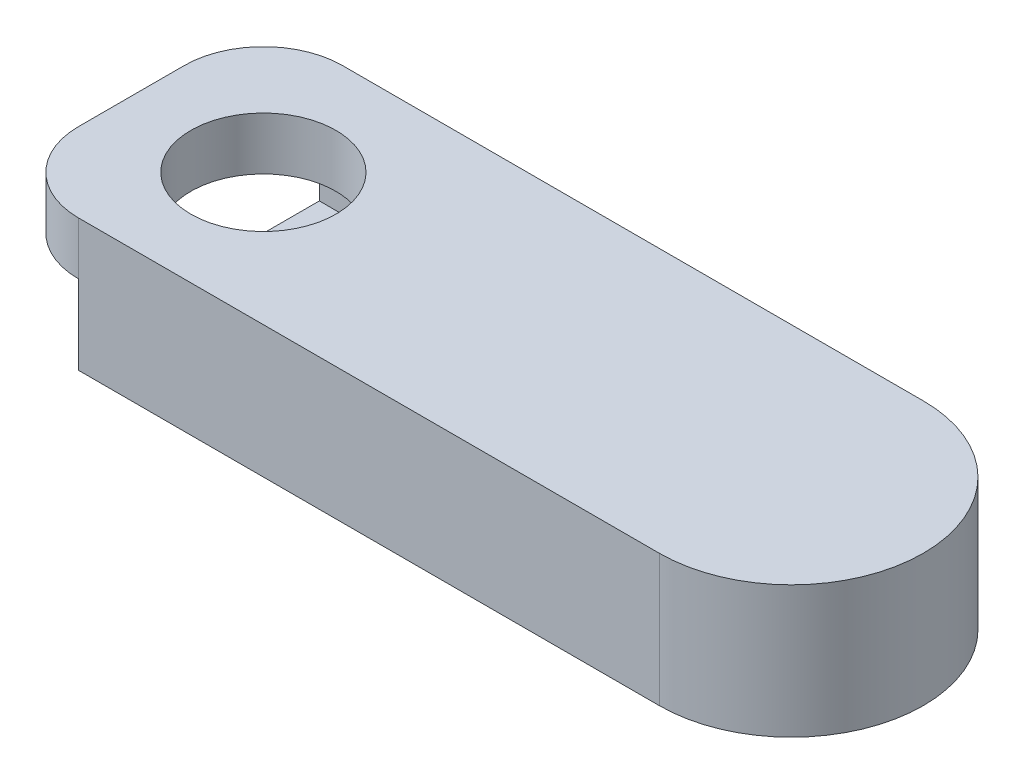
SolidWorks part; units mm, degrees
ref_plane "Front Plane" through (0, 0, 0) normal (0, 0, 1) x (1, 0, 0)
ref_plane "Top Plane" through (0, 0, 0) normal (0, 1, 0) x (1, 0, 0)
ref_plane "Right Plane" through (0, 0, 0) normal (1, 0, 0) x (0, 0, -1)
sketch "Sketch1" plane through (0, 0, 0) normal (0, 1, 0) x (1, 0, 0)
  line L0 (0, 0) -> (-381, 0)
  line L1 (-381, 0) -> (-381, -127)
  line L2 (-381, -127) -> (0, -127)
  line L3 (0, -127) -> (0, 0)
  dimension "D1" = 381
  dimension "D2" = 127
extrude "Boss-Extrude1" add sketch "Sketch1" along normal blind 25.4
fillet "Fillet1" radius 63.5 2 edges at (0, 12.7, 0) (0, 12.7, 127)
fillet "Fillet2" radius 38.1 2 edges at (-381, 12.7, 0) (-381, 12.7, 127)
sketch "Sketch2" plane through (0, 0, 0) normal (0, 1, 0) x (1, 0, 0)
  line L0 (-63.5, -12.7) -> (-342.9, -11.1592)
  line L1 (-342.9, -11.1592) -> (-342.9, 0)
  line L2 (-342.9, 0) -> (-63.5, 0)
  line L3 (-63.5, -127) -> (-342.9, -127)
  line L4 (-342.9, -127) -> (-342.9, -114.3)
  line L5 (-342.9, -114.3) -> (-63.5, -114.3)
  arc A0 (-63.5, -114.3) -> (-63.5, -12.7) centre (-63.5, -63.5) ccw
  arc A1 (-63.5, 0) -> (-63.5, -127) centre (-63.5, -63.5) cw
  arc A2 (-63.5, -127) -> (0, -63.5) centre (-63.5, -63.5) ccw construction
  dimension "D1" = 11.1592
  dimension "D3" = 12.7
  dimension "D2" = 12.7
extrude "Boss-Extrude2" add sketch "Sketch2" against normal blind 25.4
ref_plane "Plane1" through (0, -25.4, 0) normal (0, 1, 0) x (1, 0, 0)
sketch "Sketch3" plane through (0, -25.4, 0) normal (0, 1, 0) x (1, 0, 0)
  line L1 (-342.9, -127) -> (-342.9, -82.55)
  line L2 (-342.9, -114.3) -> (-342.9, -127) construction
  line L3 (-342.9, 0) -> (-342.9, -44.45)
  line L4 (-342.9, 0) -> (-63.5, 0)
  line L5 (-63.5, -44.45) -> (-342.9, -44.45)
  line L6 (-342.9, -82.55) -> (-63.5, -82.55)
  line L7 (-63.5, -127) -> (-342.9, -127)
  arc A0 (-381, -88.9) -> (-342.9, -127) centre (-342.9, -88.9) ccw construction
  arc A1 (-63.5, -127) -> (-63.5, 0) centre (-63.5, -63.5) ccw
  arc A2 (-63.5, -127) -> (-63.5, 0) centre (-63.5, -63.5) ccw construction
  arc A3 (-63.5, -82.55) -> (-63.5, -44.45) centre (-63.5, -63.5) ccw
  dimension "D1" = 44.45
  dimension "D2" = 44.45
  dimension "D3" = 279.4
extrude "Boss-Extrude3" add sketch "Sketch3" against normal blind 12.7
sketch "Sketch11" plane through (0, 25.4, 0) normal (0, 1, 0) x (1, 0, 0)
  line L0 (-381, -63.5) -> (-317.5, -63.5) construction
  line L1 (-381, -38.1) -> (-381, -88.9) construction
  circle A0 centre (-317.5, -63.5) radius 34.925
  dimension "D2" = 69.85
  dimension "D1" = 63.5
extrude "Cut-Extrude4" cut sketch "Sketch11" against normal blind 38.1
